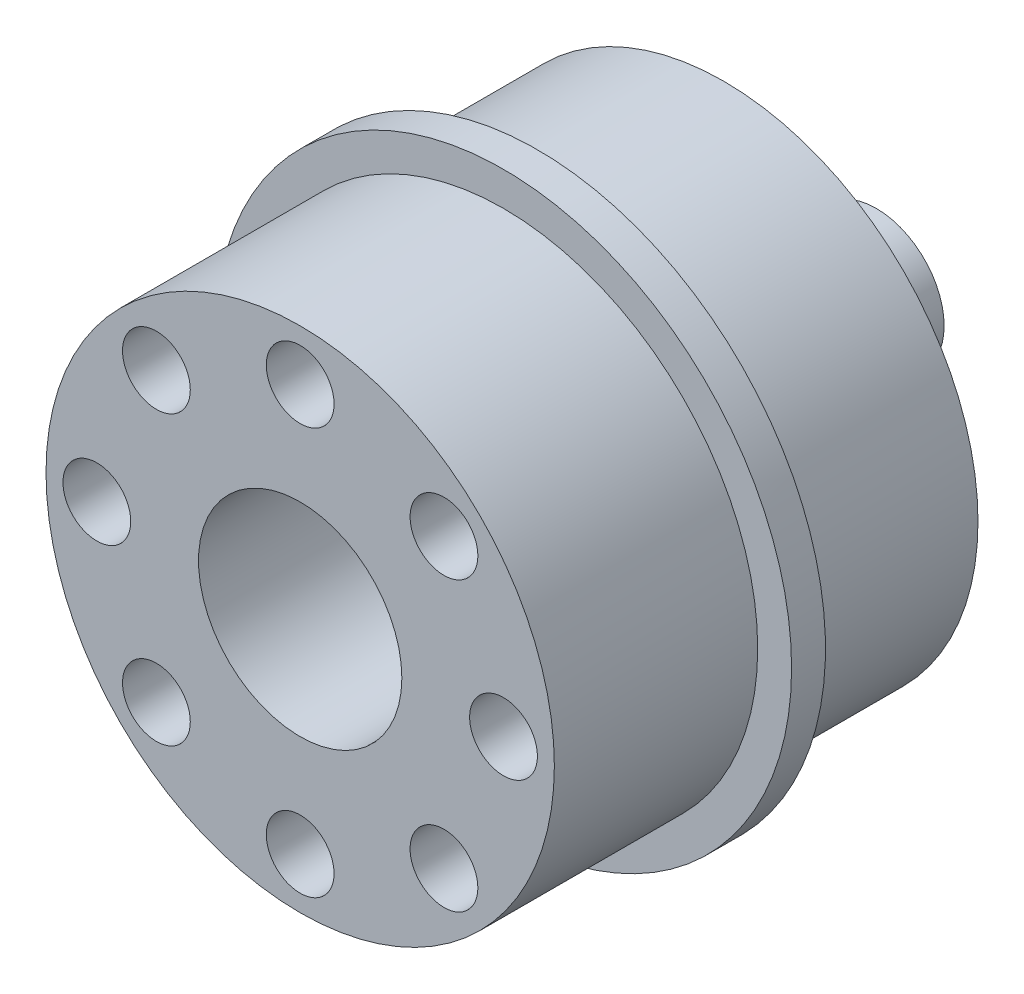
SolidWorks part; units mm, degrees
ref_plane "前视基准面" through (0, 0, 0) normal (0, 0, 1) x (1, 0, 0)
ref_plane "上视基准面" through (0, 0, 0) normal (0, 1, 0) x (1, 0, 0)
ref_plane "右视基准面" through (0, 0, 0) normal (1, 0, 0) x (0, 0, -1)
sketch "草图1" plane through (0, 0, 0) normal (0, 0, 1) x (1, 0, 0)
  circle A0 centre (0, 0) radius 17
  dimension "D1" = 34
extrude "拉伸1" add sketch "草图1" along normal blind 25
sketch "草图3" plane through (0, 0, 0) normal (0, 0, -1) x (-1, 0, 0)
  circle A0 centre (0, 0) radius 4
  dimension "D1" = 8
extrude "拉伸3" add sketch "草图3" along normal blind 9
sketch "草图4" plane through (0, 0, 0) normal (0, 0, -1) x (-1, 0, 0)
  circle A0 centre (0, 0) radius 17 construction
  circle A1 centre (0, 0) radius 17
  circle A2 centre (0, 0) radius 15
  dimension "D1" = 30
extrude "切除-拉伸1" cut sketch "草图4" against normal blind 11
sketch "草图5" plane through (0, 0, 25) normal (0, 0, 1) x (1, 0, 0)
  circle A0 centre (0, 0) radius 17 construction
  circle A1 centre (0, 0) radius 17
  circle A2 centre (0, 0) radius 15 construction
  circle A3 centre (0, 0) radius 15
extrude "切除-拉伸2" cut sketch "草图5" against normal blind 12
sketch "草图7" plane through (0, 0, 25) normal (0, 0, 1) x (1, 0, 0)
  line L0 (0, -1000) -> (0, 49000) construction
  line L1 (-1000, 0) -> (49000, 0) construction
  line L3 (-707.1068, -707.1068) -> (34648.2323, 34648.2323) construction
  line L4 (707.1068, -707.1068) -> (-34648.2323, 34648.2323) construction
  circle A0 centre (0, 0) radius 12 construction
  dimension "D1" = 24
hole_wizard "M4 螺纹孔1" positions "3D草图1" profile "草图8" tap size "M4" standard "ISO"
sketch3d "3D草图1"
  line L0 (-1000, 0, 25) -> (49000, 0, 25) construction
  line L1 (707.1068, -707.1068, 25) -> (-34648.2323, 34648.2323, 25) construction
  line L2 (0, -1000, 25) -> (0, 49000, 25) construction
  line L3 (-707.1068, -707.1068, 25) -> (34648.2323, 34648.2323, 25) construction
  circle A0 centre (0, 0, 25) radius 12 construction
  point P0 (-12, 0, 25)
  point P4 (-8.4853, 8.4853, 25)
  point P8 (0, 12, 25)
  point P12 (8.4853, 8.4853, 25)
  point P16 (12, 0, 25)
  point P18 (8.4853, -8.4853, 25)
  point P20 (-8.4853, -8.4853, 25)
  point P22 (0, -12, 25)
  point P28 (0, 0, 37)
sketch "草图8" plane through (-12, 0, 25) normal (1, 0, 0) x (0, -1, 0)
  line L0 (0, 0) -> (0, 11.0914)
  line L1 (0, 11.0914) -> (1.65, 10.1)
  line L2 (1.65, 10.1) -> (1.65, 8)
  line L3 (1.65, 8) -> (2, 8)
  line L4 (2, 8) -> (2, 0)
  line L5 (2, 0) -> (0, 0)
  line L10 (0, 11.0914) -> (-1.65, 10.1) construction
  line L11 (0, -6.35) -> (0, 107.95) construction
  dimension "蹟恇謂郰芛眻噤" = 3.3
  dimension "蹟恇謂郰芛旮僅" = 10.1
  dimension "蹟恇翋眻噤" = 4
  dimension "蹟恇旮僅" = 8
  dimension "絳芛褒僅" = 118
sketch "草图9" plane through (0, 0, 0) normal (0, 1, 0) x (1, 0, 0)
  line L0 (0, -991) -> (0, 49009) construction
  line L1 (4, 9) -> (-4, 9) construction
  line L2 (4, 0) -> (-4, 0) construction
  circle A0 centre (0, 5) radius 1.7
  point P5 (0, 9)
  dimension "D2" = 3.4
  dimension "D1" = 5
extrude "切除-拉伸3" cut sketch "草图9" against normal blind 10 and the other way blind 10
hole_wizard "M12 螺纹孔1" positions "3D草图2" profile "草图10" tap size "M12" standard "ISO"
sketch3d "3D草图2"
  point P0 (0, 0, 25)
sketch "草图10" plane through (0, 0, 25) normal (1, 0, 0) x (0, -1, 0)
  line L0 (0, 0) -> (0, 22.3144)
  line L1 (0, 22.3144) -> (5.1, 19.25)
  line L2 (5.1, 19.25) -> (5.1, 14)
  line L3 (5.1, 14) -> (6, 14)
  line L4 (6, 14) -> (6, 0)
  line L5 (6, 0) -> (0, 0)
  line L10 (0, 22.3144) -> (-5.1, 19.25) construction
  line L11 (0, -6.35) -> (0, 107.95) construction
  dimension "蹟恇謂郰芛眻噤" = 10.2
  dimension "蹟恇謂郰芛旮僅" = 19.25
  dimension "蹟恇翋眻噤" = 12
  dimension "蹟恇旮僅" = 14
  dimension "絳芛褒僅" = 118
